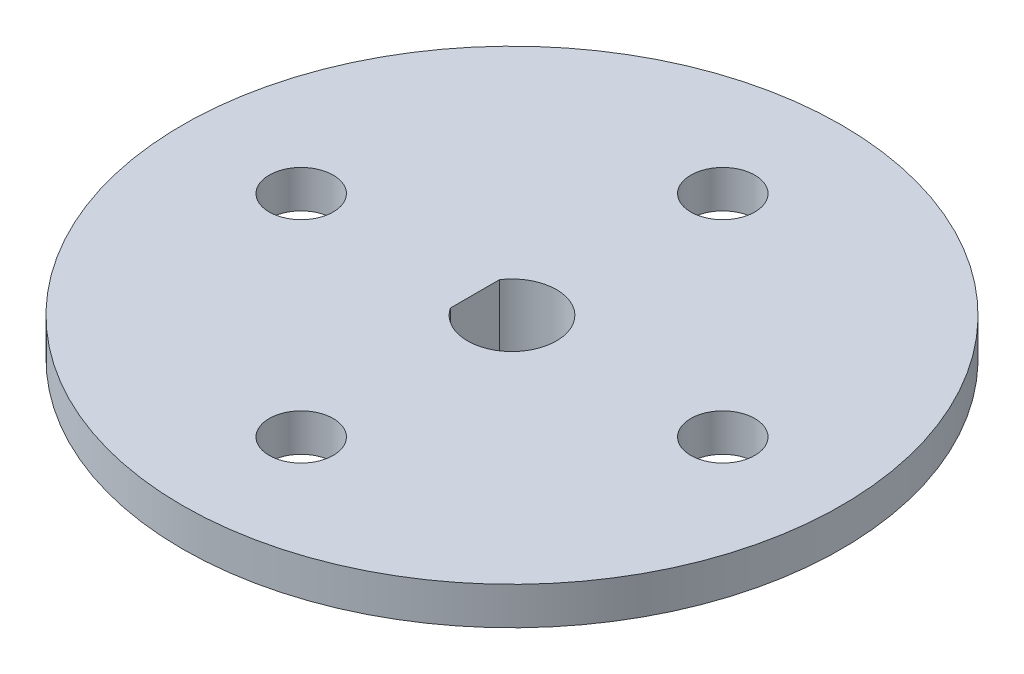
SolidWorks part; units mm, degrees
ref_plane "Front Plane" through (0, 0, 0) normal (0, 0, 1) x (1, 0, 0)
ref_plane "Top Plane" through (0, 0, 0) normal (0, 1, 0) x (1, 0, 0)
ref_plane "Right Plane" through (0, 0, 0) normal (1, 0, 0) x (0, 0, -1)
sketch "Sketch1" plane through (0, 0, 0) normal (0, 1, 0) x (1, 0, 0)
  line L0 (0, 0) -> (0, 22.225) construction
  line L1 (-2.5, 1.6583) -> (-2.5, -1.6583)
  circle A0 centre (0, 0) radius 22.225
  circle A2 centre (0, 14.2156) radius 2.159
  circle A3 centre (0, 0) radius 3
  circle A4 centre (14.2156, 0) radius 2.159
  circle A5 centre (0, -14.2156) radius 2.159
  circle A6 centre (-14.2156, 0) radius 2.159
  circle A7 centre (0, 0) radius 9.525
  point P18 (0, 0)
  dimension "D1" = 44.45
  dimension "D2" = 4.318
  dimension "D4" = 6
  dimension "D6" = 19.05
  dimension "D3" = 2.5
  dimension "D5" = 4
extrude "Boss-Extrude1" add sketch "Sketch1" along normal blind 2.54 contours A7 A2 A0 A6 A5 A4 | A3 A7 | L1 A3 region at (-2.7015, 0, 0) region at (-21.5964, 0, 0) region at (-9.2556, 0, 0)
extrude "Boss-Extrude2" add sketch "Sketch1<4>" against normal blind 2.54 contours A3 A7 | L1 A3 region at (-2.7015, 0, 0) region at (-9.2556, 0, 0)
sketch "Sketch1<4>" plane through (0, 0, 0) normal (0, 1, 0) x (1, 0, 0) same geometry as "Sketch1"
